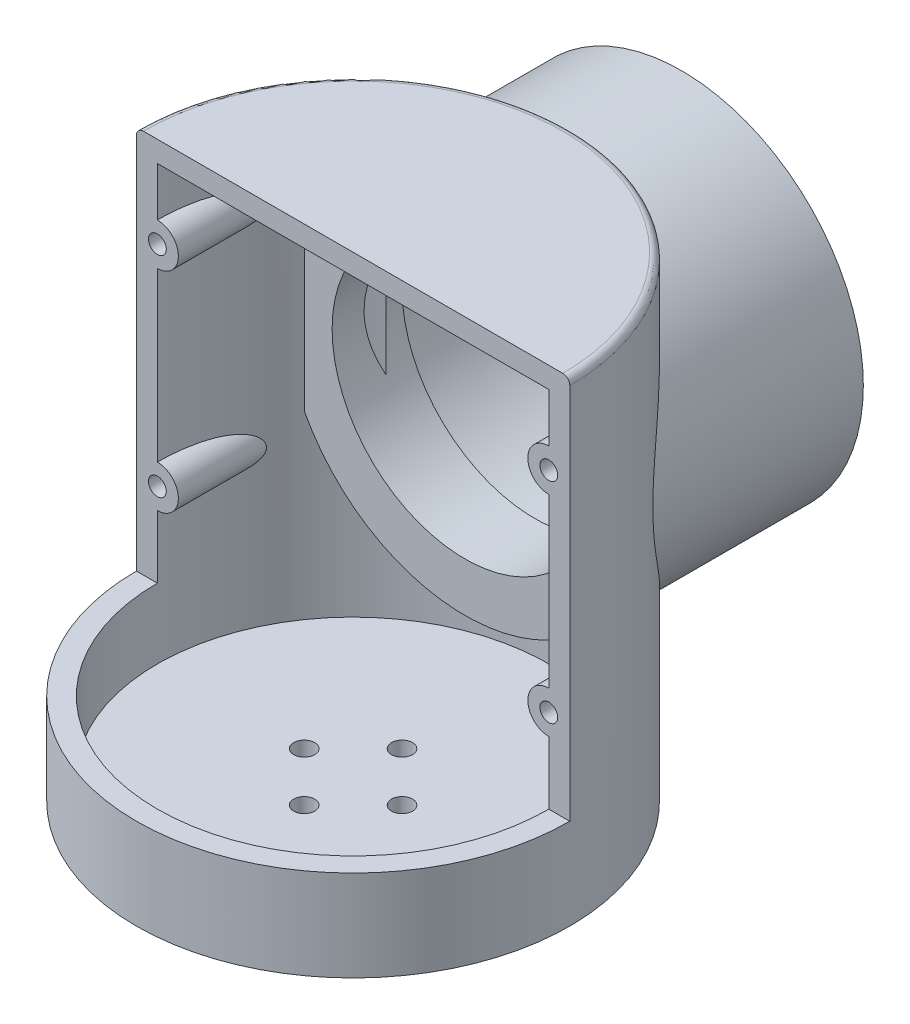
SolidWorks part; units mm, degrees
material "ABS"
ref_plane "Спереди" through (0, 0, 0) normal (0, 0, 1) x (1, 0, 0)
ref_plane "Сверху" through (0, 0, 0) normal (0, 1, 0) x (1, 0, 0)
ref_plane "Справа" through (0, 0, 0) normal (1, 0, 0) x (0, 0, -1)
sketch "Эскиз3" plane through (0, 0, 0) normal (1, 0, 0) x (0, 0, -1)
  line L0 (0, 68.2882) -> (0, 0) construction
  line L1 (0, 0) -> (31, 0)
  line L2 (31, 0) -> (31, 68)
  line L3 (31, 68) -> (0, 68)
  line L4 (0, 68) -> (0, 65)
  line L5 (0, 65) -> (28, 65)
  line L6 (28, 65) -> (28, 3)
  line L7 (28, 3) -> (0, 3)
  line L8 (0, 3) -> (0, 0)
  dimension "D1" = 62
  dimension "D2" = 68
  dimension "D3" = 3
  dimension "D4" = 3
  dimension "D5" = 3
revolve "Повернуть2" add sketch "Эскиз3" angle 360 about L0
sketch "Эскиз4" plane through (0, 68, 0) normal (0, 1, 0) x (1, 0, 0)
  line L0 (-31, 0) -> (31, 0)
  circle A0 centre (0, 0) radius 31 construction
  arc A1 (31, 0) -> (-31, 0) centre (0, 0) cw
extrude "Вырез-Вытянуть1" cut sketch "Эскиз4" against normal blind 55
sketch "Эскиз6" plane through (0, 0, 0) normal (0, -1, 0) x (1, 0, 0)
  circle A0 centre (7, 0) radius 1.5
  dimension "D1" = 3
  dimension "D2" = 7
extrude "Вырез-Вытянуть3" cut sketch "Эскиз6" against normal up to surface (3 mm away) up to face at (0, 3, 28)
pattern_circular "Круговой массив1" count 4 over 360 about axis through (0, 68.2882, 0) along (0, 1, 0) of "Вырез-Вытянуть3"
sketch "Эскиз7" plane through (0, 0, 0) normal (0, 0, 1) x (1, 0, 0)
  circle A0 centre (0, 41) radius 21
  circle A1 centre (0, 41) radius 26
  dimension "D1" = 52
  dimension "D2" = 42
  dimension "D3" = 41
extrude "Бобышка-Вытянуть1" add sketch "Эскиз7" against normal blind 31 from offset 16 offset against normal yes
sketch "Эскиз8" plane through (0, 0, -47) normal (0, 0, -1) x (-1, 0, 0)
  circle A0 centre (0, 41) radius 21
  dimension "D1" = 42
  dimension "D2" = 41
extrude "Вырез-Вытянуть4" cut sketch "Эскиз8" against normal blind 25
sketch "Эскиз11" plane through (0, 0, 0) normal (0, 0, 1) x (1, 0, 0)
  line L0 (-28, 65) -> (-28, 13) construction
  line L1 (28, 13) -> (28, 65) construction
  line L3 (-28, 25) -> (28, 25) construction
  line L4 (-28, 25) -> (-28, 55) construction
  line L5 (-28, 55) -> (28, 55) construction
  line L6 (28, 25) -> (28, 55) construction
  circle A0 centre (-28, 55) radius 3
  circle A1 centre (-28, 25) radius 3
  circle A2 centre (28, 25) radius 3
  circle A3 centre (28, 55) radius 3
  point P12 (0, 25)
  point P15 (28, 40)
  dimension "D1" = 6
  dimension "D2" = 6
  dimension "D3" = 6
  dimension "D4" = 6
  dimension "D5" = 30
  dimension "D6" = 40
extrude "Бобышка-Вытянуть3" add sketch "Эскиз11" against normal up to surface (12.6095 mm away) up to face at (0.3812, 44.067, -10.9146)
hole_wizard "Сверло под метчик  спиральное M2.52" positions "Эскиз15" profile "Эскиз16" hole size "M2.5x0.45" standard "Ansi Metric"
sketch "Эскиз15" plane through (0, 0, 0) normal (0, 0, 1) x (1, 0, 0)
  point P0 (-28, 55)
  point P3 (28, 55)
  point P6 (28, 25)
  point P9 (-28, 25)
sketch "Эскиз16" plane through (-28, 55, 0) normal (1, 0, 0) x (0, -1, 0)
  line L0 (0, 0) -> (0, 5.7661)
  line L1 (0, 5.7661) -> (1.275, 5)
  line L2 (1.275, 5) -> (1.275, 0)
  line L5 (1.275, 0) -> (0, 0)
  line L10 (0, 5.7661) -> (-1.275, 5) construction
  line L11 (0, -6.35) -> (0, 107.95) construction
  dimension "Диаметр отверстия" = 2.55
  dimension "Глубина отверстия" = 5
  dimension "Угол заточки сверла" = 118
hole_wizard "Отверстие обработанное метчиком M2x0.41" positions "Эскиз18" profile "Эскиз19" tap size "M2x0.4" standard "HASCO Metric"
sketch "Эскиз18" plane through (0, 0, -47) normal (0, 0, -1) x (-1, 0, 0)
  line L2 (0, 41) -> (23, 41) construction
  line L4 (0, 41) -> (16.2635, 57.2635) construction
  circle A1 centre (0, 41) radius 23 construction
  point P0 (16.2635, 57.2635)
  dimension "D1" = 46
  dimension "D2" = 45
sketch "Эскиз19" plane through (-16.2635, 57.2635, -47) normal (1, 0, 0) x (0, 1, 0)
  line L0 (0, 0) -> (0, 10.4807)
  line L1 (0, 10.4807) -> (0.8, 10)
  line L2 (0.8, 10) -> (0.8, 0.225)
  line L3 (0.8, 0.225) -> (1.025, 0)
  line L5 (1.025, 0) -> (0, 0)
  line L6 (-0.8, 0.225) -> (-1.025, 0) construction
  line L10 (0, 10.4807) -> (-0.8, 10) construction
  line L11 (0, -6.35) -> (0, 107.95) construction
  dimension "Диаметр сверла" = 1.6
  dimension "Глубина сверла" = 10
  dimension "Диаметр передней зенковки" = 2.05
  dimension "Угол передней зенковки" = 90
  dimension "Угол заточки сверла" = 118
cosmetic thread "Отверстие резьбы1" parameters "D1"=8, "D2"=2
pattern_circular "Круговой массив2" count 8 over 360 about axis through (0, 41, -47) along (0, 0, 1) of "Отверстие обработанное метчиком M2x0.41"
ref_plane "Плоскость1" through (0, 0, -26) normal (0, 0, -1) x (-1, 0, 0)
sketch "Эскиз20" plane through (0, 0, -26) normal (0, 0, -1) x (-1, 0, 0)
  circle A0 centre (0, 41) radius 19
  circle A1 centre (0, 41) radius 26
  dimension "D1" = 38
  dimension "D2" = 52
extrude "Бобышка-Вытянуть6" add sketch "Эскиз20" against normal blind 10 contours A1 A0 region at (25.2646, 41, -26)
fillet "Скругление1" radius 1 1 edges at (0, 68, -31)
